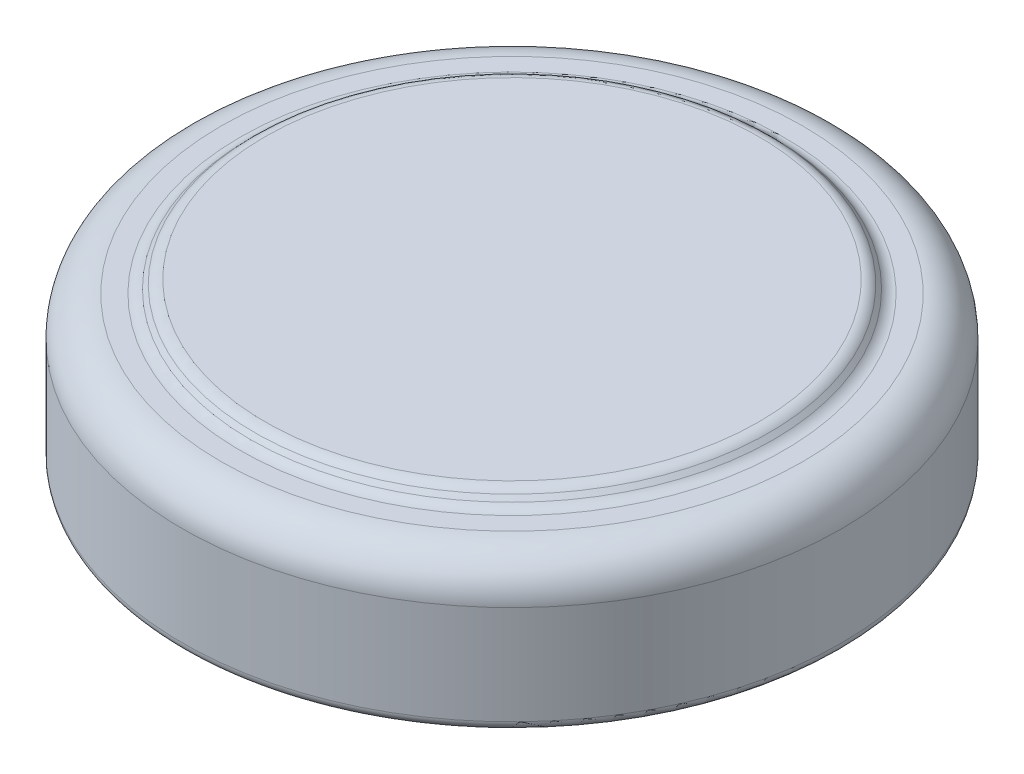
SolidWorks part; units mm, degrees
ref_plane "Front Plane" through (0, 0, 0) normal (0, 0, 1) x (1, 0, 0)
ref_plane "Top Plane" through (0, 0, 0) normal (0, 1, 0) x (1, 0, 0)
ref_plane "Right Plane" through (0, 0, 0) normal (1, 0, 0) x (0, 0, -1)
sketch "Sketch1" plane through (0, 0, 0) normal (0, 0, 1) x (1, 0, 0)
  line L0 (0, 0) -> (-3.3, 0)
  line L1 (-3.4, 0.1) -> (-3.4, 1.12)
  line L2 (-2.5479, 1.65) -> (0, 1.65)
  line L3 (0, 1.65) -> (0, 0)
  line L4 (-2.6961, 1.5639) -> (-2.6539, 1.6061)
  line L7 (-2.8021, 1.52) -> (-3, 1.52)
  arc A0 (-3.4, 1.12) -> (-3, 1.52) centre (-3, 1.12) cw
  arc A1 (-2.5479, 1.65) -> (-2.6539, 1.6061) centre (-2.5479, 1.5) ccw
  arc A2 (-2.8021, 1.52) -> (-2.6961, 1.5639) centre (-2.8021, 1.67) ccw
  arc A3 (-3.3, 0) -> (-3.4, 0.1) centre (-3.3, 0.1) cw
  point P9 (-3.4, 1.52)
  point P13 (-2.74, 1.52)
  point P17 (-3.4, 0)
  point P18 (-2.74, 1.52)
  point P20 (-2.74, 1.52)
  dimension "D6" = 0.4
  dimension "D7" = 0.15
  dimension "D8" = 0.1
  dimension "D1" = 3.4
  dimension "D2" = 1.65
  dimension "D3" = 2.74
  dimension "D4" = 1.52
  dimension "D5" = 45
revolve "Revolve1" add sketch "Sketch1" angle 360 about L3
sketch "Sketch2" plane through (0, 0, 0) normal (0, -1, 0) x (1, 0, 0)
  line L0 (0.25, 0.25) -> (1.5, 0.25)
  line L1 (-0.25, 1.5) -> (0.25, 1.5)
  line L2 (-0.25, 1.5) -> (-0.25, 0.25)
  line L3 (-0.25, -1.5) -> (0.25, -1.5)
  line L4 (0.25, 1.5) -> (0.25, 0.25)
  line L5 (-1.5, 0.25) -> (-0.25, 0.25)
  line L6 (-1.5, 0.25) -> (-1.5, -0.25)
  line L7 (-1.5, -0.25) -> (-0.25, -0.25)
  line L8 (1.5, 0.25) -> (1.5, -0.25)
  line L9 (0.25, -0.25) -> (1.5, -0.25)
  line L10 (0.25, -0.25) -> (0.25, -1.5)
  line L11 (-0.25, -0.25) -> (-0.25, -1.5)
  circle A0 centre (0, 0) radius 2 construction
  text T0 "                SR65" font "Century Gothic" height 1
  dimension "D1" = 4
  dimension "D2" = 0.5
  dimension "D3" = 0.25
  dimension "D4" = 0.5
  dimension "D5" = 0.25
  dimension "D6" = 3
  dimension "D7" = 3
  dimension "D8" = 1.5
  dimension "D9" = 1.5
wrap "Wrap1" sketch "Sketch2" wrap type scribe source sketch "Sketch2" face at (-3.3, 0, 0)
